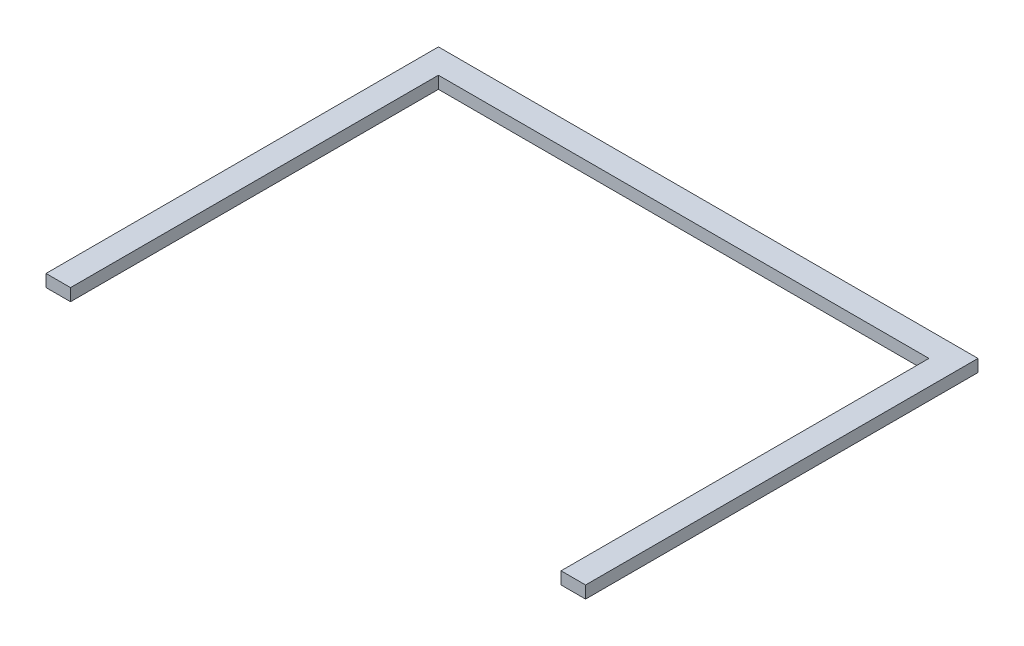
SolidWorks part; units mm, degrees
ref_plane "Front Plane" through (0, 0, 0) normal (0, 0, 1) x (1, 0, 0)
ref_plane "Top Plane" through (0, 0, 0) normal (0, 1, 0) x (1, 0, 0)
ref_plane "Right Plane" through (0, 0, 0) normal (1, 0, 0) x (0, 0, -1)
sketch "Sketch1" plane through (0, 0, 0) normal (0, 1, 0) x (1, 0, 0)
  line L0 (-127, -101.6) -> (-127, 88.9)
  line L1 (-139.7, -101.6) -> (-127, -101.6)
  line L2 (-139.7, -101.6) -> (-139.7, 101.6)
  line L3 (-139.7, 101.6) -> (139.7, 101.6)
  line L4 (139.7, -101.6) -> (139.7, 101.6)
  line L5 (-139.7, -101.6) -> (139.7, 101.6) construction
  line L6 (-139.7, 101.6) -> (139.7, -101.6) construction
  line L7 (-127, 88.9) -> (127, 88.9)
  line L8 (127, -101.6) -> (127, 88.9)
  line L9 (127, -101.6) -> (139.7, -101.6)
  point P0 (0, 0)
  dimension "D1" = 279.4
  dimension "D2" = 203.2
  dimension "D3" = 12.7
extrude "Boss-Extrude1" add sketch "Sketch1" against normal blind 6.35 contours L0 L7 L8 L9 L4 L3 L2 L1
